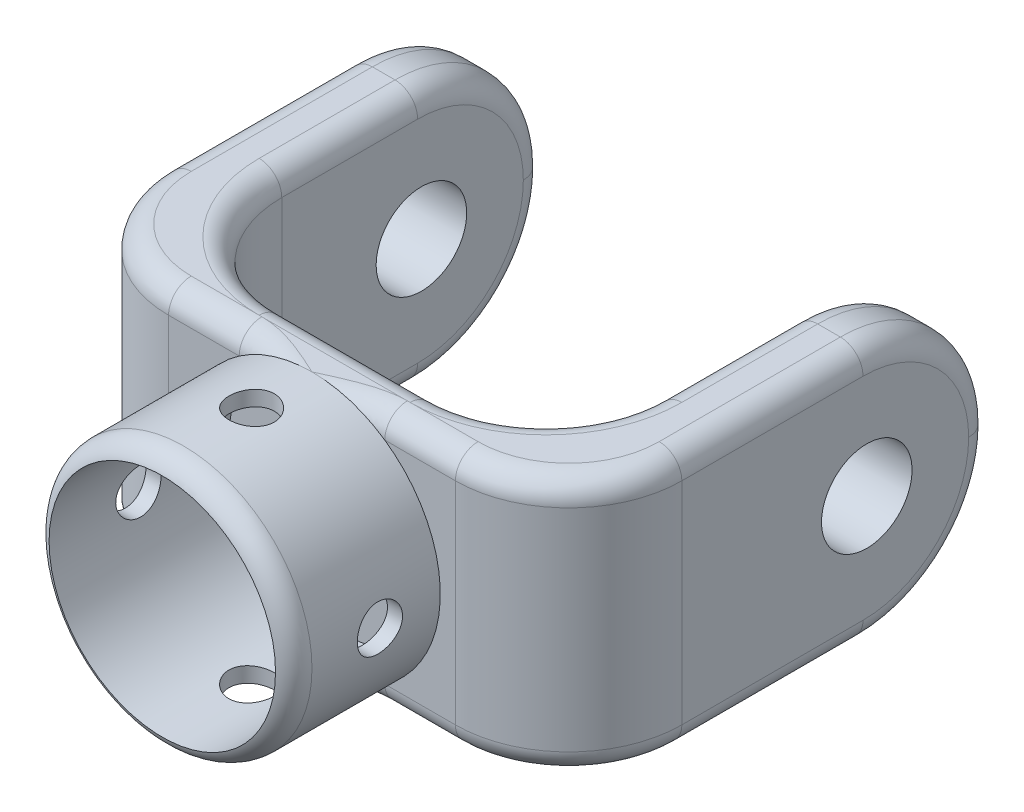
SolidWorks part; units mm, degrees
ref_plane "Front Plane" through (0, 0, 0) normal (0, 0, 1) x (1, 0, 0)
ref_plane "Top Plane" through (0, 0, 0) normal (0, 1, 0) x (1, 0, 0)
ref_plane "Right Plane" through (0, 0, 0) normal (1, 0, 0) x (0, 0, -1)
sketch "Sketch1" plane through (0, 0, 0) normal (0, 1, 0) x (1, 0, 0)
  line L0 (-8.3333, 0) -> (8.3333, 0)
  line L1 (8.3333, 0) -> (8.3333, 16.6667)
  line L2 (8.3333, 16.6667) -> (11.3333, 16.6667)
  line L3 (11.3333, 16.6667) -> (11.3333, -2)
  line L4 (11.3333, -2) -> (-11.3333, -2)
  line L5 (0, -2) -> (0, 0) construction
  line L6 (-11.3333, 16.6667) -> (-11.3333, -2)
  line L7 (-8.3333, 16.6667) -> (-11.3333, 16.6667)
  line L8 (-8.3333, 0) -> (-8.3333, 16.6667)
  dimension "D1" = 11.3333
  dimension "D2" = 2
  dimension "D3" = 18.6667
  dimension "D4" = 3
extrude "Boss-Extrude1" add sketch "Sketch1" along normal mid plane 11.3333
fillet "Fillet1" radius 5.6667 4 edges at (-9.8333, 5.6667, -16.6667) (-9.8333, -5.6667, -16.6667) (9.8333, 5.6667, -16.6667) (9.8333, -5.6667, -16.6667)
sketch "Sketch3" plane through (0, 0, 2) normal (0, 0, 1) x (1, 0, 0)
  circle A0 centre (0, 0) radius 5.6667
  dimension "D1" = 11.3333
extrude "Boss-Extrude2" add sketch "Sketch3" along normal blind 6.6667
fillet "Fillet3" radius 1 1 edges at (5.6667, 0, 8.6667)
fillet "Fillet4" radius 5 4 edges at (-8.3333, 0, 0) (8.3333, 0, 0) (-11.3333, 0, 2) (11.3333, 0, 2)
fillet "Fillet5" radius 1 30 edges at (11.3333, -5.6667, -7) (11.3333, -4.0069, -15.0069) (11.3333, 4.0069, -15.0069) (11.3333, 5.6667, -7) (9.8689, 5.6667, 0.5355) (3.1667, 5.6667, 2) (-3.1667, 5.6667, 2) (-9.8689, 5.6667, 0.5355) (-11.3333, 5.6667, -7) (-11.3333, 4.0069, -15.0069) (-11.3333, -4.0069, -15.0069) (-11.3333, -5.6667, -7) (-9.8689, -5.6667, 0.5355) (-3.1667, -5.6667, 2) (3.1667, -5.6667, 2) (6.8689, -5.6667, -1.4645) (8.3333, -5.6667, -8) (8.3333, -4.0069, -15.0069) (8.3333, 4.0069, -15.0069) (8.3333, 5.6667, -8) (6.8689, 5.6667, -1.4645) (0, 5.6667, 0) (-6.8689, 5.6667, -1.4645) (-8.3333, 5.6667, -8) (-8.3333, 4.0069, -15.0069) (-8.3333, -4.0069, -15.0069) (-8.3333, -5.6667, -8) (-6.8689, -5.6667, -1.4645) (9.8689, -5.6667, 0.5355) (0, -5.6667, 0)
sketch "Sketch4" plane through (-11.3333, 0, 0) normal (-1, 0, 0) x (0, 0, 1)
  circle A0 centre (-11.1667, 0) radius 2
  dimension "D1" = 4
  dimension "D2" = 5.5
extrude "Cut-Extrude1" cut sketch "Sketch4" against normal blind 24.6667
sketch "Sketch5" plane through (0, 0, 8.6667) normal (0, 0, 1) x (1, 0, 0)
  circle A0 centre (0, 0) radius 5
  dimension "D1" = 10
sketch "Sketch6" plane through (0, 0, 8.6667) normal (0, 0, 1) x (1, 0, 0)
  circle A0 centre (0, 0) radius 5
  dimension "D1" = 10
extrude "Cut-Extrude2" cut sketch "Sketch6" against normal blind 8
sketch "Sketch8" plane through (0, 0, 0) normal (0, 1, 0) x (1, 0, 0)
  line L0 (-5, -0.6667) -> (5, -0.6667) construction
  line L1 (-5, -0.6667) -> (5, -0.6667) construction
  circle A0 centre (0, -4.6667) radius 1
  point P4 (0, 0)
  dimension "D1" = 2
  dimension "D2" = 4
extrude "Cut-Extrude3" cut sketch "Sketch8" against normal blind 10
pattern_circular "CirPattern1" count 4 over 360 about axis through (0, 0, 8.6667) along (0, 0, -1) of "Cut-Extrude3"
